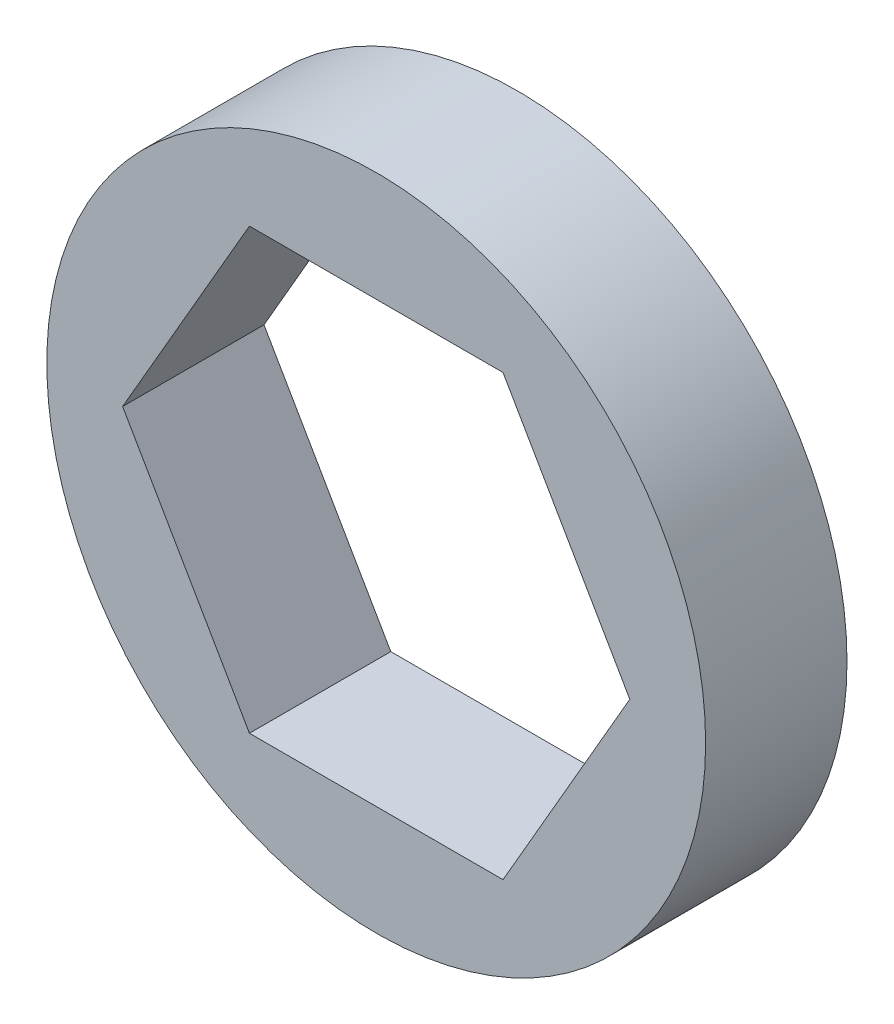
SolidWorks part; units mm, degrees
material "Nylon 101"
ref_plane "Front Plane" through (0, 0, 0) normal (0, 0, 1) x (1, 0, 0)
ref_plane "Top Plane" through (0, 0, 0) normal (0, 1, 0) x (1, 0, 0)
ref_plane "Right Plane" through (0, 0, 0) normal (1, 0, 0) x (0, 0, -1)
sketch "Sketch1" plane through (0, 0, 0) normal (0, 0, 1) x (1, 0, 0)
  line L1 (3.6662, 6.35) -> (-3.6662, 6.35)
  line L2 (-3.6662, 6.35) -> (-7.3323, 0)
  line L3 (-7.3323, 0) -> (-3.6662, -6.35)
  line L4 (-3.6662, -6.35) -> (3.6662, -6.35)
  line L5 (3.6662, -6.35) -> (7.3323, 0)
  line L6 (7.3323, 0) -> (3.6662, 6.35)
  circle A1 centre (0, 0) radius 9.525
  circle A2 centre (0, 0) radius 6.35 construction
  dimension "D1" = 19.05
  dimension ".5" = 12.7
extrude "Boss-Extrude1" add sketch "Sketch1" along normal blind 4.0876
